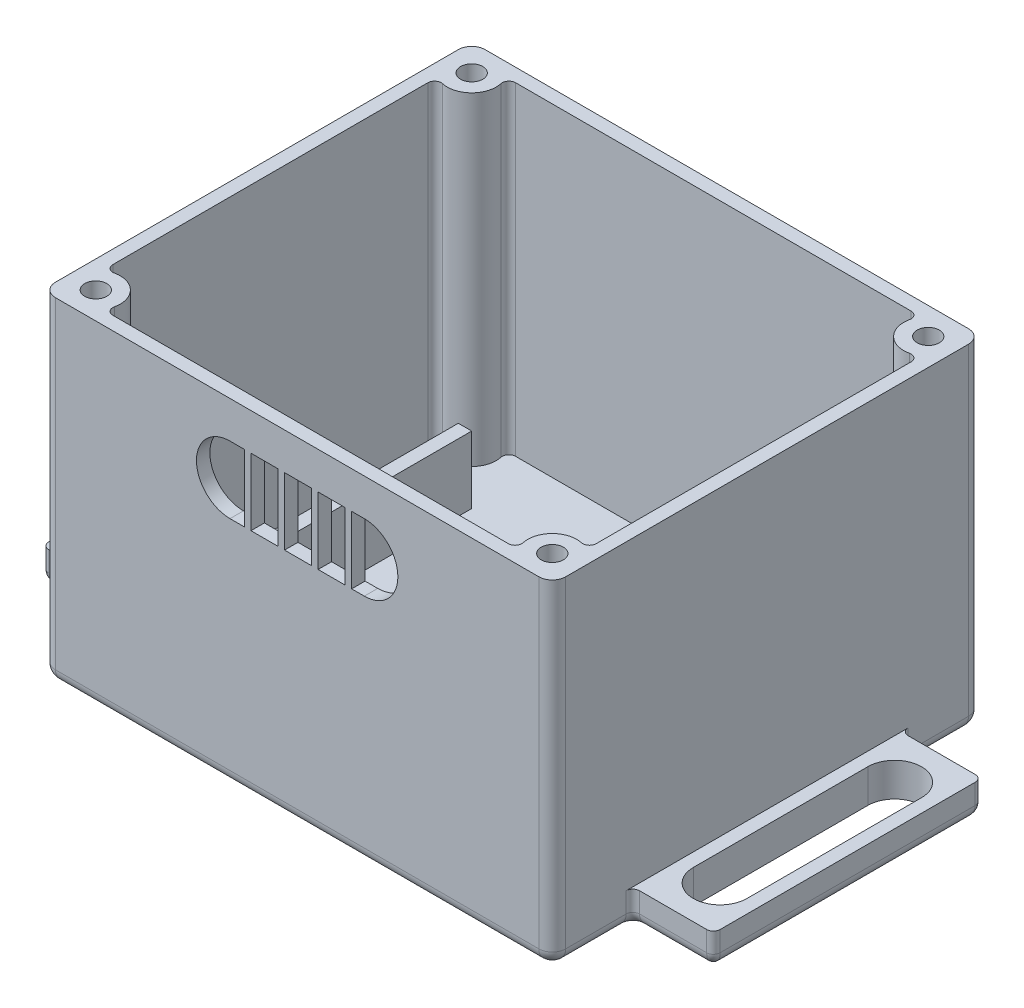
SolidWorks part; units mm, degrees
ref_plane "Piano frontale" through (0, 0, 0) normal (0, 0, 1) x (1, 0, 0)
ref_plane "Piano superiore" through (0, 0, 0) normal (0, 1, 0) x (1, 0, 0)
ref_plane "Piano destro" through (0, 0, 0) normal (1, 0, 0) x (0, 0, -1)
sketch "Schizzo1" plane through (0, 0, 0) normal (0, 1, 0) x (1, 0, 0)
  line L1 (-38, 32) -> (38, 32)
  line L2 (-38, 32) -> (-38, -32)
  line L3 (-38, -32) -> (38, -32)
  line L4 (38, 32) -> (38, -32)
  line L5 (-38, 32) -> (38, -32) construction
  line L6 (-38, -32) -> (38, 32) construction
  point P0 (0, 0)
  dimension "D1" = 76
  dimension "D2" = 64
extrude "Estrusione-Estrusione1" add sketch "Schizzo1" along normal blind 50
sketch "Schizzo2" plane through (0, 50, 0) normal (0, 1, 0) x (1, 0, 0)
  line L0 (38, 32) -> (-38, 32) construction
  line L1 (-36, 30) -> (36, 30)
  line L2 (-36, 30) -> (-36, -30)
  line L3 (-36, -30) -> (36, -30)
  line L4 (36, 30) -> (36, -30)
  line L5 (-36, 30) -> (36, -30) construction
  line L6 (-36, -30) -> (36, 30) construction
  line L8 (38, -32) -> (38, 32) construction
  point P0 (0, 0)
  dimension "D1" = 2
  dimension "D2" = 2
extrude "Taglio-Estrusione1" cut sketch "Schizzo2" against normal offset from surface (48.2 mm away) 1.8 up to face at (0, 0, 0)
sketch "Schizzo5" plane through (0, 1.8, 0) normal (0, 1, 0) x (1, 0, 0)
  line L2 (-46.9015, 0) -> (56.9538, 0) construction
  line L3 (0, 27.1281) -> (0, -29.0474) construction
  line L5 (38, 32) -> (-38, 32) construction
  line L6 (-38, 32) -> (-38, -32) construction
  line L7 (-36, 30) -> (-36, 24.9467)
  line L8 (-36, -30) -> (-36, 30) construction
  line L9 (-36, 30) -> (-30.9467, 30)
  line L10 (36, 30) -> (-36, 30) construction
  line L11 (36, 30) -> (30.9467, 30)
  line L12 (36, 30) -> (36, 24.9467)
  line L13 (36, -30) -> (36, -24.9467)
  line L14 (36, -30) -> (30.9467, -30)
  line L15 (-36, -30) -> (-36, -24.9467)
  line L16 (-36, -30) -> (-30.9467, -30)
  circle A0 centre (-34, 28) radius 1.65
  circle A1 centre (-34, 28) radius 3.65
  circle A3 centre (34, 28) radius 1.65
  circle A5 centre (34, 28) radius 3.65
  circle A6 centre (34, -28) radius 1.65
  circle A8 centre (34, -28) radius 3.65
  circle A9 centre (-34, -28) radius 3.65
  circle A10 centre (-34, -28) radius 1.65
  line M2 (36, -30) -> (36, 30)
  line M3 (36, 30) -> (-36, 30)
  line M4 (-36, 30) -> (-36, -30)
  line M5 (-36, -30) -> (36, -30)
  dimension "D1" = 3.3
  dimension "D4" = 2
  dimension "D2" = 4
  dimension "D3" = 4
extrude "Estrusione-Estrusione2" add sketch "Schizzo5" along normal through all contours A0 M3 M4 | A5 A3 M2 M3 | A8 A6 M2 M5 | A9 A10 M4 M5 region at (-33.4734, 1.8, -29.9201) region at (-32.3027, 1.8, 24.8592) region at (33.4734, 1.8, -29.9201) region at (31.4756, 1.8, 25.4756)
sketch "Schizzo6" plane through (0, 1.8, 0) normal (0, 1, 0) x (1, 0, 0)
  line L0 (-26, -23) -> (-26, 22)
  line L13 (-26, 22) -> (26, 22)
  line L14 (26, 22) -> (26, -23)
  line L15 (26, -23) -> (24, -23)
  line L16 (24, -23) -> (24, 20)
  line L17 (24, 20) -> (-24, 20)
  line L18 (-24, 20) -> (-24, -23)
  line L19 (-24, -23) -> (-26, -23)
  line L20 (0, 43.6943) -> (0, -44.2648) construction
  line L21 (38, 32) -> (-38, 32) construction
  circle A0 centre (-33, 18) radius 1.25
  circle A1 centre (-33, -8) radius 1.25
  circle A2 centre (33, -8) radius 1.25
  circle A3 centre (33, 18) radius 1.25
  point P8 (0, 20)
  dimension "D7" = 2.5
  dimension "D1" = 2
  dimension "D2" = 45
  dimension "D3" = 52
  dimension "D4" = 2
  dimension "D5" = 20
  dimension "D6" = 26
  dimension "D8" = 14
  dimension "D9" = 66
extrude "Taglio-Estrusione2" cut sketch "Schizzo6" against normal through all contours A0 | A3 | A2 | A1 region at (-33, 1.8, -18) region at (33, 1.8, 8) region at (33, 1.8, -18)
sketch "Schizzo7" plane through (0, 1.8, 0) normal (0, 1, 0) x (1, 0, 0)
  line L0 (0, 41.8493) -> (0, -45.2549) construction
  line L1 (-28, -25) -> (-28, 20)
  line L7 (-26, 20) -> (-26, -25)
  line L8 (-26, -25) -> (-28, -25)
  line L9 (-28, 20) -> (-26, 20)
  line L11 (28, -25) -> (28, 20)
  line L12 (26, -25) -> (28, -25)
  line L13 (26, 20) -> (26, -25)
  line L14 (28, 20) -> (26, 20)
  line L15 (30.9467, 30) -> (-30.9467, 30) construction
  dimension "D1" = 45
  dimension "D2" = 26
  dimension "D3" = 10
  dimension "D5" = 2
extrude "Estrusione-Estrusione4" add sketch "Schizzo7" along normal blind 10
sketch "Schizzo8" plane through (0, 0, 32) normal (0, 0, 1) x (1, 0, 0)
  line L0 (38, 50) -> (38, 0) construction
  line L1 (-38, 0) -> (38, 0) construction
  line L2 (-10, 39.5) -> (10, 39.5) construction
  line L3 (-10, 44.5) -> (10, 44.5)
  line L4 (-10, 34.5) -> (10, 34.5)
  arc A1 (-10, 44.5) -> (-10, 34.5) centre (-10, 39.5) ccw
  arc A2 (10, 34.5) -> (10, 44.5) centre (10, 39.5) ccw
  point P8 (0, 39.5)
  dimension "D1" = 20
  dimension "D4" = 10
  dimension "D5" = 28
  dimension "D6" = 39.5
extrude "Taglio-Estrusione3" cut sketch "Schizzo8" against normal up to next
sketch "Schizzo9" plane through (0, 0, 0) normal (0, -1, 0) x (1, 0, 0)
  line L0 (-38, -32) -> (-38, 32) construction
  line L1 (-50, 20) -> (-38, 20)
  line L2 (-50, 20) -> (-50, -20)
  line L3 (-50, -20) -> (-38, -20)
  line L4 (-38, 20) -> (-38, -20)
  line L5 (-50, 20) -> (-38, -20) construction
  line L6 (-50, -20) -> (-38, 20) construction
  line L7 (-44, -13) -> (-44, 13) construction
  line L8 (-48, -13) -> (-48, 13)
  line L9 (-40, -13) -> (-40, 13)
  line L10 (0, 22.541) -> (0, -19.4532) construction
  line L11 (44, -13) -> (44, 13) construction
  line L12 (48, -13) -> (48, 13)
  line L13 (40, -13) -> (40, 13)
  line L14 (50, -20) -> (38, -20)
  line L15 (38, 20) -> (38, -20)
  line L16 (50, 20) -> (38, 20)
  line L17 (50, 20) -> (50, -20)
  arc A0 (-48, -13) -> (-40, -13) centre (-44, -13) ccw
  arc A1 (-40, 13) -> (-48, 13) centre (-44, 13) ccw
  arc A2 (48, -13) -> (40, -13) centre (44, -13) cw
  arc A3 (40, 13) -> (48, 13) centre (44, 13) cw
  point P0 (-44, 0)
  point P9 (-44, 0)
  point P19 (44, 0)
  dimension "D1" = 12
  dimension "D2" = 40
  dimension "D3" = 8
  dimension "D4" = 26
extrude "Estrusione-Estrusione5" add sketch "Schizzo9" against normal blind 5
fillet "Raccordo3" radius 1 8 edges at (38, 2.5, -20) (50, 2.5, -20) (50, 2.5, 20) (38, 2.5, 20) (-38, 2.5, -20) (-50, 2.5, -20) (-38, 2.5, 20) (-50, 2.5, 20)
fillet "Raccordo1" radius 2 24 edges at (-38, 25, -32) (-38, 0, -26.5) (-38, 0, 26.5) (0, 0, -32) (38, 0, -26.5) (38, 0, 26.5) (0, 0, 32) (-38, 25, 32) (38, 25, -32) (38, 25, 32) (-38.2929, 0, 20.2929) (-44, 0, 20) (-49.7071, 0, 19.7071) (-50, 0, 0) (-49.7071, 0, -19.7071) (-44, 0, -20) (-38.2929, 0, -20.2929) (38.2929, 0, -20.2929) (44, 0, -20) (49.7071, 0, -19.7071) (50, 0, 0) (49.7071, 0, 19.7071) (44, 0, 20) (38.2929, 0, 20.2929)
fillet "Raccordo2" radius 1 8 edges at (30.9467, 25.9, -30) (36, 25.9, -24.9467) (36, 25.9, 24.9467) (30.9467, 25.9, 30) (-30.9467, 25.9, 30) (-36, 25.9, 24.9467) (-36, 25.9, -24.9467) (-30.9467, 25.9, -30)
sketch "Schizzo12" plane through (0, 34.5, 0) normal (0, 1, 0) x (1, 0, 0)
  line L0 (-7.8807, -32) -> (-7.8807, -30)
  line L1 (-10, -32) -> (10, -32) construction
  line L2 (10, -30) -> (-10, -30) construction
  line L3 (-7.8807, -30) -> (-6.8807, -30)
  line L4 (-6.8807, -30) -> (-6.8807, -32)
  line L5 (-6.8807, -32) -> (-7.8807, -32)
  line L6 (-2.8807, -30) -> (-1.8807, -30)
  line L7 (29.4588, -30) -> (-29.4588, -30) construction
  line L8 (-1.8807, -30) -> (-1.8807, -32)
  line L9 (-1.8807, -32) -> (-2.8807, -32)
  line L10 (-2.8807, -32) -> (-2.8807, -30)
  line L11 (2.1193, -32) -> (2.1193, -30)
  line L12 (-36, -32) -> (36, -32) construction
  line L13 (-29.4588, -30) -> (29.4588, -30) construction
  line L14 (2.1193, -30) -> (3.1193, -30)
  line L15 (3.1193, -30) -> (3.1193, -32)
  line L16 (3.1193, -32) -> (2.1193, -32)
  line L17 (7.1193, -30) -> (8.1193, -30)
  line L18 (8.1193, -30) -> (8.1193, -32)
  line L19 (8.1193, -32) -> (7.1193, -32)
  line L20 (7.1193, -32) -> (7.1193, -30)
  point P26 (7.1193, -31)
  dimension "D1" = 1
  dimension "D2" = 4
  dimension "D3" = 4
  dimension "D4" = 4
extrude "Estrusione-Estrusione6" add sketch "Schizzo12" along normal up to next
